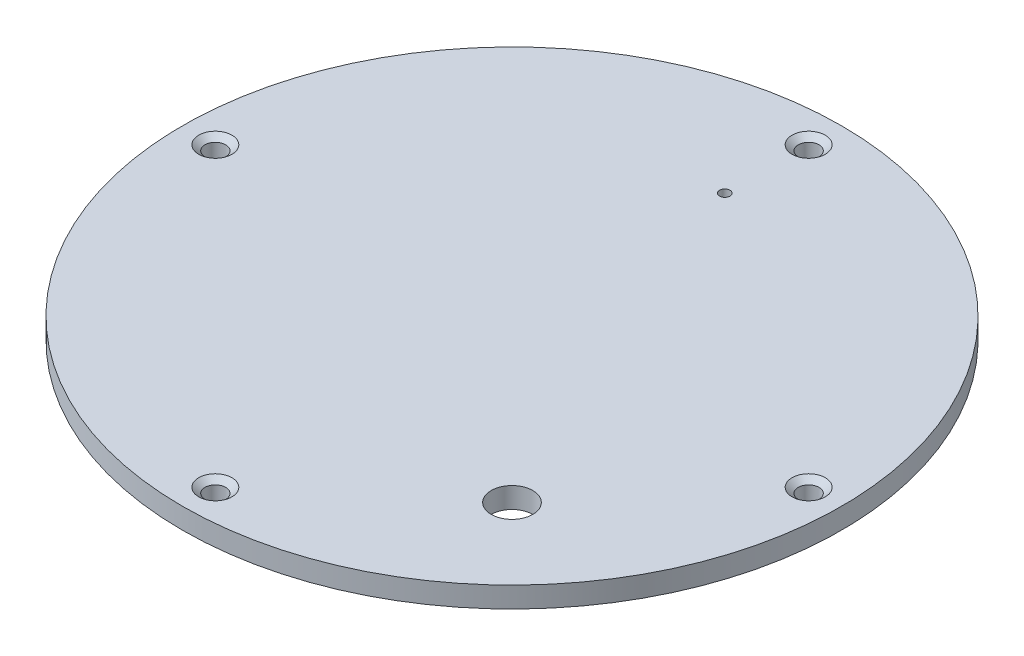
SolidWorks part; units mm, degrees
material "1060 Alloy"
ref_plane "Front Plane" through (0, 0, 0) normal (0, 0, 1) x (1, 0, 0)
ref_plane "Top Plane" through (0, 0, 0) normal (0, 1, 0) x (1, 0, 0)
ref_plane "Right Plane" through (0, 0, 0) normal (1, 0, 0) x (0, 0, -1)
sketch "Sketch1" plane through (0, 0, 0) normal (0, 1, 0) x (1, 0, 0)
  circle A0 centre (0, 0) radius 15.875
  dimension "D1" = 31.75
extrude "Boss-Extrude1" add sketch "Sketch1" along normal blind 1
sketch "Sketch6" plane through (0, 1, 0) normal (0, 1, 0) x (1, 0, 0)
  line L0 (0, 0) -> (14.1535, -14.1535) construction
  line L1 (0, 0) -> (17.9741, 0) construction
  circle A0 centre (0, 10.25) radius 0.25
  circle A1 centre (7.7782, -7.7782) radius 1
  dimension "D1" = 10.25
  dimension "D3" = 0.5
  dimension "D4" = 2
  dimension "D2" = 0
  dimension "D5" = 11
  dimension "D6" = 45
extrude "Cut-Extrude1" cut sketch "Sketch6" against normal through all both and the other way through all
hole_wizard "CSK for M2 Flat Head Machine Screw1" positions "Sketch7" profile "Sketch8" countersink size "M2" standard "ANSI Metric" end condition through all
sketch "Sketch7" plane through (0, 1, 0) normal (0, 1, 0) x (1, 0, 0)
  point P0 (0, 14.29)
  point P2 (-14.29, 0)
  point P4 (0, -14.29)
  point P6 (14.29, 0)
  dimension "D1" = 14.29
  dimension "D2" = 14.29
  dimension "D3" = 14.29
  dimension "D4" = 14.29
sketch "Sketch8" plane through (0, 1, -14.29) normal (1, 0, 0) x (0, 0, 1)
  line L0 (0, 0) -> (0, 1)
  line L1 (0, 1) -> (0.5, 1)
  line L2 (0.5, 1) -> (0.5, 0.2517)
  line L3 (0.5, 0.2517) -> (0.8, 0)
  line L5 (0.8, 0) -> (0, 0)
  line L6 (-0.5, 0.2517) -> (-0.8, 0) construction
  line L11 (0, -6.35) -> (0, 107.95) construction
  dimension "Thru Hole Dia." = 1
  dimension "Thru Hole Depth" = 1
  dimension "Near C'Sink Dia." = 1.6
  dimension "Near C'Sink Angle" = 100
